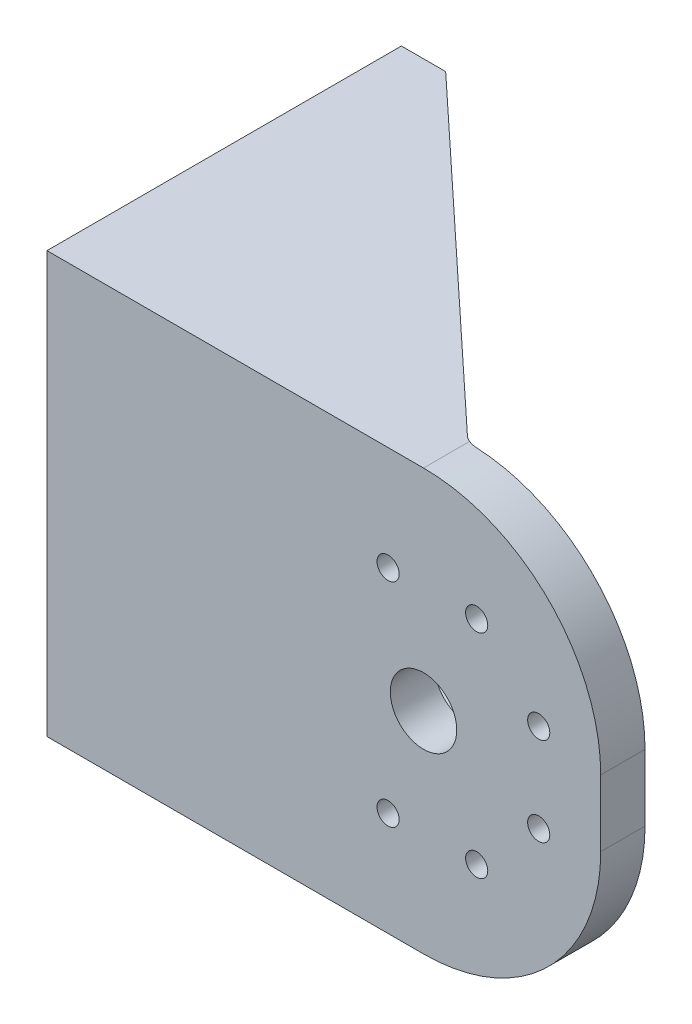
SolidWorks part; units mm, degrees
ref_plane "Front Plane" through (0, 0, 0) normal (0, 0, 1) x (1, 0, 0)
ref_plane "Top Plane" through (0, 0, 0) normal (0, 1, 0) x (1, 0, 0)
ref_plane "Right Plane" through (0, 0, 0) normal (1, 0, 0) x (0, 0, -1)
sketch "Sketch3" plane through (0, 0, 0) normal (0, 0, 1) x (1, 0, 0)
  line L6 (68.6171, 80.0599) -> (153.6171, 80.0599)
  line L10 (68.6171, 80.0599) -> (68.6171, -14.9401)
  line L36 (-101.4371, 49.8561) -> (-17.2351, 49.8561) construction
  line L70 (68.6171, -14.9401) -> (153.6171, -14.9401)
  line L71 (193.6171, 40.0599) -> (193.6171, 25.0599)
  circle A22 centre (153.6171, 32.5599) radius 7.5
  circle A23 centre (179.6171, 42.5599) radius 2.5
  circle A24 centre (145.6171, 56.5599) radius 2.5
  circle A25 centre (165.6171, 56.5599) radius 2.5
  circle A26 centre (145.6171, 8.5599) radius 2.5
  circle A27 centre (165.6171, 8.5599) radius 2.5
  circle A28 centre (179.6171, 22.5599) radius 2.5
  arc A29 (153.6171, -14.9401) -> (193.6171, 25.0599) centre (153.6171, 25.0599) ccw
  arc A30 (153.6171, 80.0599) -> (193.6171, 40.0599) centre (153.6171, 40.0599) cw
  point P23 (193.6171, 80.0599)
  dimension "D2" = 5
  dimension "D3" = 10
  dimension "D4" = 26
  dimension "D7" = 5
  dimension "D21" = 125
  dimension "D22" = 40
  dimension "D23" = 47.5
  dimension "D1" = 15
  dimension "D5" = 5
  dimension "D6" = 5
  dimension "D8" = 5
  dimension "D9" = 5
  dimension "D24" = 40
  dimension "D10" = 8
  dimension "D11" = 24
  dimension "D12" = 20
  dimension "D15" = 20
  dimension "D16" = 8
  dimension "D17" = 20
  dimension "D18" = 48
  dimension "D19" = 48
  dimension "D20" = 95
  dimension "D13" = 26
  dimension "D14" = 24
extrude "Boss-Extrude1" add sketch "Sketch3" along normal blind 10
sketch "Sketch4" plane through (0, 0, 0) normal (0, 0, -1) x (-1, 0, 0)
  line L0 (-68.6171, -14.9401) -> (-153.6171, -14.9401) construction
  line L1 (-68.6171, 80.0599) -> (-78.6171, 80.0599)
  line L2 (-68.6171, 80.0599) -> (-68.6171, -14.9401)
  line L3 (-68.6171, -14.9401) -> (-78.6171, -14.9401)
  line L4 (-78.6171, 80.0599) -> (-78.6171, -14.9401)
  dimension "D1" = 10
extrude "Boss-Extrude2" add sketch "Sketch4" along normal blind 70
sketch "Sketch8" plane through (68.6171, 0, 0) normal (-1, 0, 0) x (0, 0, 1)
  line L0 (10, 80.0599) -> (-70, 80.0599) construction
  line L1 (-40, 32.5599) -> (-56.1679, 25.863) construction
  line L2 (-70, 32.5599) -> (0, 32.5599) construction
  line L3 (-70, -14.9401) -> (-70, 80.0599) construction
  circle A0 centre (-40, 32.5599) radius 7.5
  circle A1 centre (-56.1679, 25.863) radius 2.5
  circle A2 centre (-56.1679, 39.2569) radius 2.5
  circle A3 centre (-46.697, 48.7278) radius 2.5
  circle A4 centre (-33.303, 48.7278) radius 2.5
  circle A5 centre (-23.8321, 39.2569) radius 2.5
  circle A6 centre (-23.8321, 25.863) radius 2.5
  circle A7 centre (-33.303, 16.392) radius 2.5
  circle A8 centre (-46.697, 16.392) radius 2.5
  point P27 (-40, 32.5599)
  dimension "D1" = 15
  dimension "D6" = 5
  dimension "D2" = 47.5
  dimension "D3" = 30
  dimension "D4" = 17.5
  dimension "D5" = 22.5
  dimension "D7" = 8
extrude "Cut-Extrude2" cut sketch "Sketch8" against normal blind 43.8
sketch "Sketch9" plane through (0, -14.9401, 0) normal (0, -1, 0) x (1, 0, 0)
  line L0 (78.6171, -70) -> (153.6171, 0)
  line L1 (52.25, 0) -> (-52.25, 0) construction
  line L2 (78.6171, 0) -> (153.6171, 0) construction
  line L3 (78.6171, -70) -> (78.6171, 0)
  line L4 (78.6171, 0) -> (153.6171, 0)
extrude "Boss-Extrude3" add sketch "Sketch9" against normal blind 10
ref_plane "Plane1" through (0, 32.5599, 0) normal (0, -1, 0) x (-1, 0, 0)
mirror "Mirror1" about plane through (0, 32.5599, 0) normal (0, -1, 0) of "Boss-Extrude3"
fillet "Fillet1" radius 5 2 edges at (153.6171, 75.0599, 0) (153.6171, -9.9401, 0)
